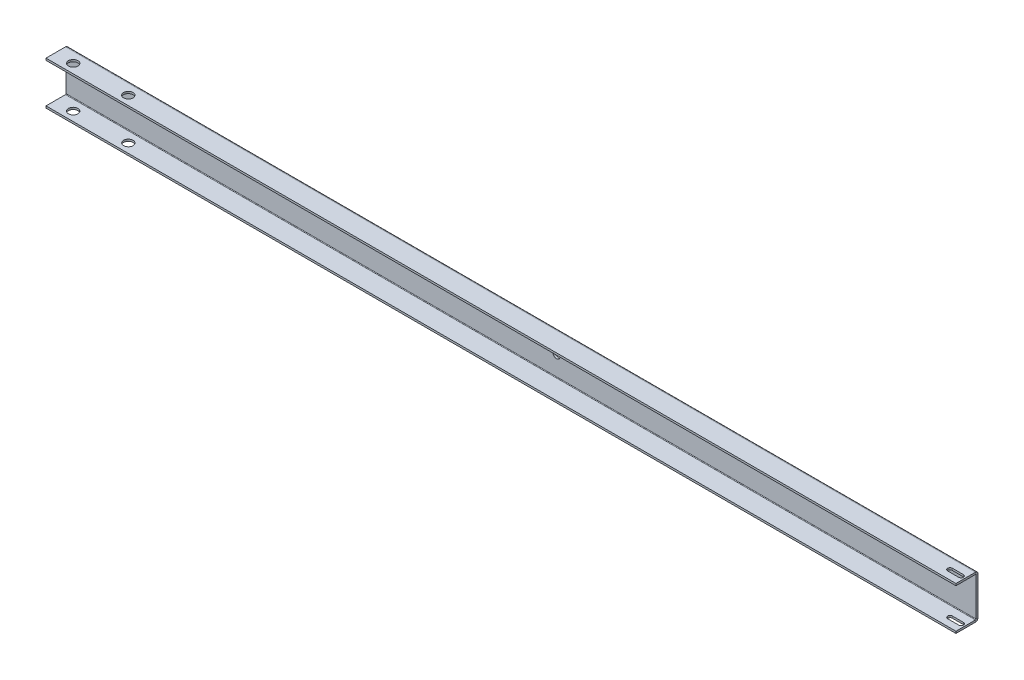
SolidWorks part; units mm, degrees
note: The reader was unsure of these and kept them because the rebuilt part matched: flange length of "Edge-Flange1".
material "ASTM A36 Steel"
ref_plane "Front Plane" through (0, 0, 0) normal (0, 0, 1) x (1, 0, 0)
ref_plane "Top Plane" through (0, 0, 0) normal (0, 1, 0) x (1, 0, 0)
ref_plane "Right Plane" through (0, 0, 0) normal (1, 0, 0) x (0, 0, -1)
sketch "Sketch1" plane through (0, 0, 0) normal (0, 0, 1) x (1, 0, 0)
  line L1 (-577.5, -27.5) -> (577.5, -27.5)
  line L2 (-577.5, -27.5) -> (-577.5, 27.5)
  line L3 (-577.5, 27.5) -> (577.5, 27.5)
  line L4 (577.5, -27.5) -> (577.5, 27.5)
  line L5 (-577.5, -27.5) -> (577.5, 27.5) construction
  line L6 (-577.5, 27.5) -> (577.5, -27.5) construction
  point P0 (0, 0)
  dimension "D1" = 1155
  dimension "D2" = 55
base flange "Base-Flange1" sketch "Sketch1" thickness 2.5 reverse thickness direction no parameters "D1"=0.7366
edge flange "Edge-Flange1" sketch "Sketch10" flange profiles "Sketch10", "Sketch11" flange angle 90 flange length 28 flange position material inside bend radius 0.7366 thickness 2.5 relief rectangular parameters "D6"=10, "D8"=1
sketch "Sketch10" plane through (0, 27.5, 0) normal (0, 1, 0) x (-1, 0, 0)
  line L0 (-577.5, 0) -> (577.5, 0) construction
  line L1 (-577.5, 0) -> (577.5, 0)
  line L2 (-577.5, 0) -> (-577.5, 25.5)
  line L3 (-577.5, 25.5) -> (577.5, 25.5)
  line L4 (577.5, 25.5) -> (577.5, 0)
sketch "Sketch11" plane through (0, -27.5, 0) normal (0, -1, 0) x (1, 0, 0)
  line L0 (-577.5, 0) -> (577.5, 0) construction
  line L1 (-577.5, 0) -> (577.5, 0)
  line L2 (-577.5, 0) -> (-577.5, 25.5)
  line L3 (-577.5, 25.5) -> (577.5, 25.5)
  line L4 (577.5, 25.5) -> (577.5, 0)
bend "EdgeBend1" bend radius 0.7366 bend angle 90 parameters "D5"=1
bend "EdgeBend2" bend radius 0.7366 bend angle 90 parameters "D5"=2
sketch "Sketch12" plane through (0, 27.5, 0) normal (0, 1, 0) x (1, 0, 0)
  line L0 (572.5, -14) -> (558.5, -14) construction
  line L1 (572.5, -17) -> (558.5, -17)
  line L2 (572.5, -11) -> (558.5, -11)
  line L3 (577.5, -25.5) -> (577.5, -0.7366) construction
  line L4 (-577.5, -25.5) -> (577.5, -25.5) construction
  arc A0 (572.5, -17) -> (572.5, -11) centre (572.5, -14) ccw
  arc A1 (558.5, -11) -> (558.5, -17) centre (558.5, -14) ccw
  point P2 (565.5, -14)
  dimension "D1" = 3
  dimension "D3" = 5
  dimension "D2" = 14
  dimension "D4" = 11.5
extrude "Cut-Extrude1" cut sketch "Sketch12" against normal through all both and the other way through all normal cut yes
sketch "Sketch13" plane through (0, 27.5, 0) normal (0, 1, 0) x (1, 0, 0)
  line L0 (-577.5, -25.5) -> (577.5, -25.5) construction
  line L1 (-577.5, -0.7366) -> (-577.5, -25.5) construction
  circle A0 centre (-554.5, -14) radius 6
  dimension "D1" = 12
  dimension "D2" = 11.5
  dimension "D3" = 23
extrude "Cut-Extrude2" cut sketch "Sketch13" against normal through all both and the other way through all normal cut yes
pattern_linear "LPattern1" count 2 spacing 70 along (1, 0, 0) of "Cut-Extrude2"
sketch "Sketch14" plane through (0, 0, 0) normal (0, 0, 1) x (1, 0, 0)
  line L0 (577.5, -24.2634) -> (577.5, 24.2634) construction
  circle A0 centre (44.9385, 0) radius 4.5
  dimension "D1" = 9
  dimension "D2" = 532.5615
extrude "Cut-Extrude3" cut sketch "Sketch14" against normal blind 10 normal cut yes
sketch "Bend-Lines1" [suppressed] plane through (0, 0, 0) normal (0, 1, 0) x (1, 0, 0)
sketch "Bounding-Box1" [suppressed] plane through (0, 0, 0) normal (0, 1, 0) x (1, 0, 0)
sheet metal parameters "Sheet-Metal1" thickness 2.5 parameters "D1"=0.7366
flat pattern "Flat-Pattern1" [suppressed]
sketch "Bend-Lines2" plane through (0, 0, 0) normal (0, 1, 0) x (1, 0, 0)
sketch3d "Bounding-Box2" [suppressed]
  line L0 (577.5, -27.5, 0) -> (-577.5, -27.5, 0) construction
  line L1 (577.5, 27.5, 0) -> (-577.5, 27.5, 0) construction
  line L2 (577.5, -27.5, 0) -> (577.5, 27.5, 0) construction
  line L3 (-577.5, -27.5, 0) -> (-577.5, 27.5, 0) construction
sheet metal parameters "Sheet-Metal2" thickness 2.5 parameters "D1"=0.7366
flat pattern "Flat-Pattern1"
sketch "Bend-Lines2" plane through (0, 0, 0) normal (0, 0, 1) x (1, 0, 0)
  line L0 (-577.5, -25.8237) -> (577.5, -25.8237) construction
  line L1 (577.5, 25.8237) -> (-577.5, 25.8237) construction
  line L2 (-577.5, -25.8237) -> (577.5, -25.8237) construction
  line L3 (577.5, 25.8237) -> (-577.5, 25.8237) construction
sketch3d "Bounding-Box2" [suppressed]
  line L0 (-577.5, -52.1473, 0) -> (577.5, -52.1473, 0) construction
  line L1 (-577.5, 52.1473, 0) -> (577.5, 52.1473, 0) construction
  line L2 (-577.5, -52.1473, 0) -> (-577.5, 52.1473, 0) construction
  line L3 (577.5, -52.1473, 0) -> (577.5, 52.1473, 0) construction
bend of the flat pattern "Flatten-<EdgeBend1>1"
bend of the flat pattern "Flatten-<EdgeBend2>1"
sheet metal parameters "Sheet-Metal3" thickness 2.5 parameters "D1"=0.7366
flat pattern "Flat-Pattern1"
sketch "Bend-Lines2" plane through (0, 0, 0) normal (0, 0, 1) x (1, 0, 0)
  line L0 (-577.5, -25.8237) -> (577.5, -25.8237) construction
  line L1 (577.5, 25.8237) -> (-577.5, 25.8237) construction
  line L2 (-577.5, -25.8237) -> (577.5, -25.8237) construction
  line L3 (577.5, 25.8237) -> (-577.5, 25.8237) construction
sketch3d "Bounding-Box2" [suppressed]
  line L0 (-577.5, -52.1473, 0) -> (577.5, -52.1473, 0) construction
  line L1 (-577.5, 52.1473, 0) -> (577.5, 52.1473, 0) construction
  line L2 (-577.5, -52.1473, 0) -> (-577.5, 52.1473, 0) construction
  line L3 (577.5, -52.1473, 0) -> (577.5, 52.1473, 0) construction
bend of the flat pattern "Flatten-<EdgeBend1>1"
bend of the flat pattern "Flatten-<EdgeBend2>1"
sheet metal parameters "Sheet-Metal4" thickness 2.5 parameters "D1"=0.7366
flat pattern "Flat-Pattern1"
sketch "Bend-Lines2" plane through (0, 0, 0) normal (0, 0, 1) x (1, 0, 0)
  line L0 (-577.5, -25.8237) -> (577.5, -25.8237) construction
  line L1 (577.5, 25.8237) -> (-577.5, 25.8237) construction
  line L2 (-577.5, -25.8237) -> (577.5, -25.8237) construction
  line L3 (577.5, 25.8237) -> (-577.5, 25.8237) construction
sketch3d "Bounding-Box2" [suppressed]
  line L0 (-577.5, -52.1473, 0) -> (577.5, -52.1473, 0) construction
  line L1 (-577.5, 52.1473, 0) -> (577.5, 52.1473, 0) construction
  line L2 (-577.5, -52.1473, 0) -> (-577.5, 52.1473, 0) construction
  line L3 (577.5, -52.1473, 0) -> (577.5, 52.1473, 0) construction
bend of the flat pattern "Flatten-<EdgeBend1>1"
bend of the flat pattern "Flatten-<EdgeBend2>1"
sheet metal parameters "Sheet-Metal5" thickness 2.5 parameters "D1"=0.7366
flat pattern "Flat-Pattern1"
sketch "Bend-Lines2" plane through (0, 0, 0) normal (0, 0, 1) x (1, 0, 0)
  line L0 (-577.5, -25.8237) -> (577.5, -25.8237) construction
  line L1 (577.5, 25.8237) -> (-577.5, 25.8237) construction
  line L2 (-577.5, -25.8237) -> (577.5, -25.8237) construction
  line L3 (577.5, 25.8237) -> (-577.5, 25.8237) construction
sketch3d "Bounding-Box2" [suppressed]
  line L0 (-577.5, -52.1473, 0) -> (577.5, -52.1473, 0) construction
  line L1 (-577.5, 52.1473, 0) -> (577.5, 52.1473, 0) construction
  line L2 (-577.5, -52.1473, 0) -> (-577.5, 52.1473, 0) construction
  line L3 (577.5, -52.1473, 0) -> (577.5, 52.1473, 0) construction
bend of the flat pattern "Flatten-<EdgeBend1>1"
bend of the flat pattern "Flatten-<EdgeBend2>1"
sheet metal parameters "Sheet-Metal6" thickness 2.5 parameters "D1"=0.7366
flat pattern "Flat-Pattern1"
sketch "Bend-Lines2" plane through (0, 0, 0) normal (0, 0, 1) x (1, 0, 0)
  line L0 (-577.5, -25.8237) -> (577.5, -25.8237) construction
  line L1 (577.5, 25.8237) -> (-577.5, 25.8237) construction
  line L2 (-577.5, -25.8237) -> (577.5, -25.8237) construction
  line L3 (577.5, 25.8237) -> (-577.5, 25.8237) construction
sketch3d "Bounding-Box2" [suppressed]
  line L0 (-577.5, -52.1473, 0) -> (577.5, -52.1473, 0) construction
  line L1 (-577.5, 52.1473, 0) -> (577.5, 52.1473, 0) construction
  line L2 (-577.5, -52.1473, 0) -> (-577.5, 52.1473, 0) construction
  line L3 (577.5, -52.1473, 0) -> (577.5, 52.1473, 0) construction
bend of the flat pattern "Flatten-<EdgeBend1>1"
bend of the flat pattern "Flatten-<EdgeBend2>1"
